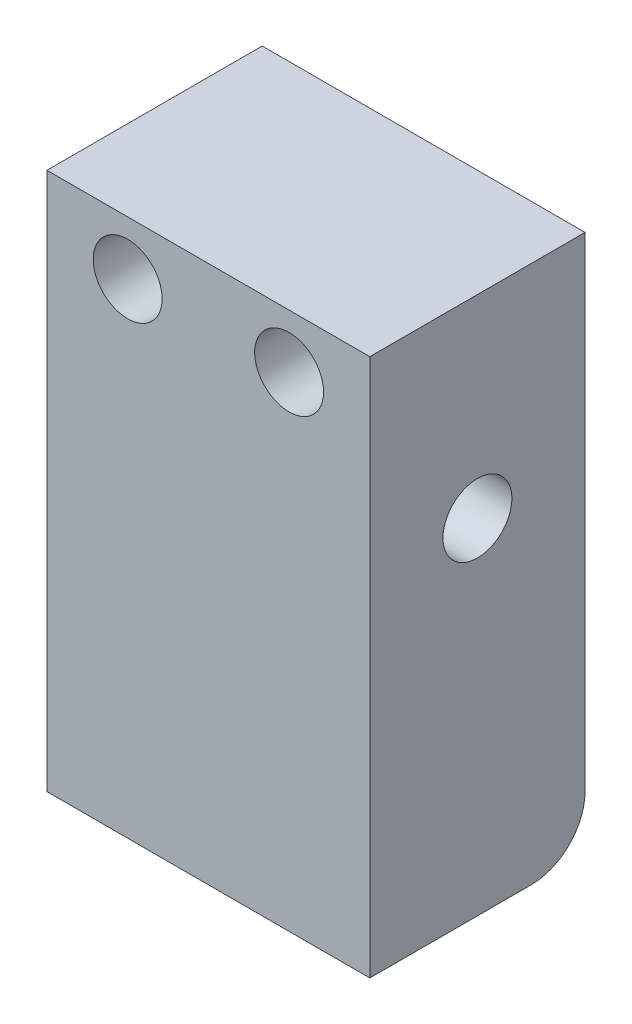
SolidWorks part; units mm, degrees
ref_plane "Front Plane" through (0, 0, 0) normal (0, 0, 1) x (1, 0, 0)
ref_plane "Top Plane" through (0, 0, 0) normal (0, 1, 0) x (1, 0, 0)
ref_plane "Right Plane" through (0, 0, 0) normal (1, 0, 0) x (0, 0, -1)
sketch "Sketch1" plane through (0, 0, 0) normal (0, 0, 1) x (1, 0, 0)
  line L0 (0, 28.575) -> (19.05, 28.575) construction
  line L1 (0, 0) -> (19.05, 0)
  line L2 (0, 0) -> (0, 31.75)
  line L3 (0, 31.75) -> (19.05, 31.75)
  line L4 (19.05, 0) -> (19.05, 31.75)
  circle A0 centre (4.7625, 28.575) radius 2.032
  circle A1 centre (14.2875, 28.575) radius 2.032
  point P14 (9.525, 31.75)
  dimension "D3" = 4.064
  dimension "D1" = 31.75
  dimension "D2" = 19.05
  dimension "D4" = 3.175
  dimension "D5" = 4.7625
  dimension "D6" = 4.7625
extrude "Boss-Extrude1" add sketch "Sketch1" along normal blind 12.7
sketch "Sketch2" plane through (0, 0, 0) normal (-1, 0, 0) x (0, 0, 1)
  line L1 (12.7, 31.75) -> (0, 31.75) construction
  line L2 (12.7, 31.75) -> (12.7, 0) construction
  circle A1 centre (6.35, 20.32) radius 2.032
  dimension "D2" = 6.35
  dimension "D3" = 4.064
  dimension "D1" = 11.43
extrude "Cut-Extrude1" cut sketch "Sketch2" against normal through all
fillet "Fillet1" radius 3.175 1 edges at (9.525, 0, 0)
